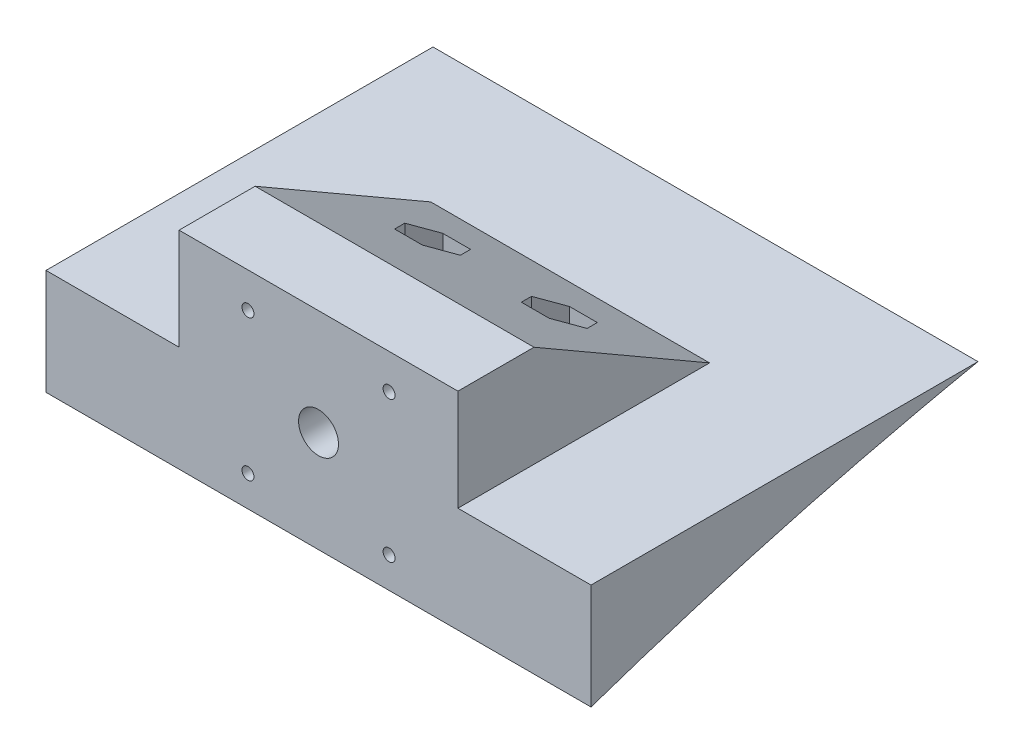
SolidWorks part; units mm, degrees
material "ABS"
ref_plane "Front Plane" through (0, 0, 0) normal (0, 0, 1) x (1, 0, 0)
ref_plane "Top Plane" through (0, 0, 0) normal (0, 1, 0) x (1, 0, 0)
ref_plane "Right Plane" through (0, 0, 0) normal (1, 0, 0) x (0, 0, -1)
curve "Curve1"
  spline degree 3 poles (0, 0.0012, 1.0003) (0, 0.0015, 0.9994) (0, 0.0028, 0.9958) (0, 0.0055, 0.9879) (0, 0.0099, 0.9747) (0, 0.0159, 0.9565) (0, 0.0233, 0.9333) (0, 0.0318, 0.9054) (0, 0.0411, 0.8731) (0, 0.051, 0.8366) (0, 0.0612, 0.7964) (0, 0.0713, 0.7528) (0, 0.0811, 0.7063) (0, 0.0903, 0.6574) (0, 0.0985, 0.6067) (0, 0.1057, 0.5546) (0, 0.1115, 0.5018) (0, 0.1158, 0.4488) (0, 0.1186, 0.3959) (0, 0.1189, 0.3436) (0, 0.1164, 0.2927) (0, 0.1112, 0.2442) (0, 0.1037, 0.1988) (0, 0.0942, 0.157) (0, 0.0831, 0.1194) (0, 0.0711, 0.0865) (0, 0.0584, 0.0585) (0, 0.0457, 0.0357) (0, 0.0334, 0.0184) (0, 0.0218, 0.0064) (0, 0.0108, -0.0005) (0, -0.0003, -0.0011) (0, -0.0092, 0.0055) (0, -0.0148, 0.017) (0, -0.0185, 0.0329) (0, -0.0204, 0.0533) (0, -0.0208, 0.0781) (0, -0.0198, 0.107) (0, -0.0176, 0.1398) (0, -0.0147, 0.176) (0, -0.0111, 0.2153) (0, -0.0074, 0.2574) (0, -0.0037, 0.3019) (0, -0.0005, 0.3484) (0, 0.002, 0.397) (0, 0.0037, 0.4471) (0, 0.0055, 0.4983) (0, 0.0069, 0.5496) (0, 0.0079, 0.6006) (0, 0.0085, 0.6505) (0, 0.0086, 0.699) (0, 0.0083, 0.7455) (0, 0.0076, 0.7894) (0, 0.0065, 0.8302) (0, 0.0053, 0.8675) (0, 0.0039, 0.9007) (0, 0.0027, 0.9296) (0, 0.0013, 0.9539) (0, 0.0006, 0.9727) (0, -0.0011, 0.9872) (0, 0, 0.9944) (0, -0.002, 0.9999) (0, -0.0005, 1) (0, 0, 1) knots 0 0 0 0 0.001372 0.005465 0.012235 0.021602 0.033461 0.047671 0.064081 0.082496 0.102719 0.124527 0.147676 0.171913 0.196978 0.222597 0.248497 0.274385 0.300041 0.32569 0.350525 0.37428 0.396711 0.417577 0.436654 0.453744 0.46868 0.481329 0.491631 0.499616 0.505546 0.510185 0.514824 0.520702 0.528516 0.538466 0.550543 0.564643 0.580638 0.598345 0.617584 0.638174 0.659922 0.682632 0.706121 0.730727 0.7557 0.780732 0.805564 0.829932 0.85357 0.876213 0.89761 0.917519 0.935698 0.951943 0.966047 0.97784 0.987174 0.993932 0.998018 0.999386 1 1 1 1
sketch "Sketch1" plane through (0, 0, 0) normal (1, 0, 0) x (0, 0, -1)
  line L3 (195.725, 0) -> (-195.725, 0) construction
  line L4 (71.5374, 26.4626) -> (-25.4, 26.4626)
  line L5 (-25.4, 26.4626) -> (-25.4, 0)
  spline S1 degree 3 poles (-25.4, 0) (-25.0834, 0.108) (-23.8218, 0.5382) (-20.9978, 1.5029) (-16.3151, 3.0589) (-6.5282, 6.2519) (9.8573, 11.2778) (28.9301, 16.5496) (47.1199, 21.0862) (60.1793, 24.0716) (68.4583, 25.8283) (71.5374, 26.4626) knots 0 0 0 0 0.001372 0.005465 0.012235 0.021602 0.047671 0.082496 0.102719 0.124527 0.137416 0.137416 0.137416 0.137416
  dimension "D1" = 26.4626
  dimension "D2" = 25.4
  dimension "D3" = 96.9374
extrude "Boss-Extrude1" add sketch "Sketch1" along normal mid plane 136.525
sketch "Sketch4" plane through (0, 0, 25.4) normal (0, 0, 1) x (1, 0, 0)
  line L0 (68.2625, 26.4626) -> (-68.2625, 26.4626) construction
  line L1 (-34.925, 51.8626) -> (34.925, 51.8626)
  line L2 (-34.925, 51.8626) -> (-34.925, 26.4626)
  line L3 (-34.925, 26.4626) -> (34.925, 26.4626)
  line L4 (34.925, 51.8626) -> (34.925, 26.4626)
  point P6 (0, 26.4626)
  dimension "D1" = 25.4
  dimension "D2" = 69.85
extrude "Boss-Extrude2" add sketch "Sketch4" against normal blind 50.8
sketch "Sketch2" plane through (0, 26.4626, 0) normal (0, 1, 0) x (1, 0, 0)
  line L0 (-68.2625, 19.05) -> (68.2625, 19.05) construction
  line L1 (-68.2625, 71.5374) -> (-68.2625, -25.4) construction
  line L2 (68.2625, 71.5374) -> (68.2625, -25.4) construction
  line L3 (-15.875, 19.05) -> (-15.875, 71.5374) construction
  line L4 (68.2625, 71.5374) -> (-68.2625, 71.5374) construction
  line L5 (15.875, 19.05) -> (15.875, 71.5374) construction
  line L6 (-68.2625, -286.8403) -> (-15.875, -286.8403) construction
  line L7 (-15.875, -286.8403) -> (15.875, -286.8403) construction
  line L8 (15.875, -286.8403) -> (68.2625, -286.8403) construction
  line L9 (-34.925, -25.4) -> (-68.2625, -25.4) construction
  circle A0 centre (-15.875, 19.05) radius 3.175
  circle A1 centre (15.875, 19.05) radius 3.175
  dimension "D1" = 6.35
  dimension "D2" = 6.35
  dimension "D3" = 31.75
  dimension "D4" = 44.45
extrude "Cut-Extrude1" cut sketch "Sketch2" against normal through all and the other way through all
sketch "Sketch5" plane through (0, 0, 25.4) normal (0, 0, 1) x (1, 0, 0)
  line L0 (68.2625, 0) -> (-68.2625, 0) construction
  circle A0 centre (0, 25.4) radius 5
  dimension "D1" = 10
  dimension "D2" = 25.4
extrude "Cut-Extrude2" cut sketch "Sketch5" against normal blind 12.7
sketch "Sketch6" plane through (0, 0, 25.4) normal (0, 0, 1) x (1, 0, 0)
  line L0 (0, 25.4) -> (27.6134, 53.0134) construction
  line L1 (0, 25.4) -> (45.1172, 25.4) construction
  circle A0 centre (17.6777, 43.0777) radius 1.5
  dimension "D1" = 3
  dimension "D2" = 25
  dimension "D3" = 45
extrude "Cut-Extrude3" cut sketch "Sketch6" against normal blind 6.35
pattern_circular "CirPattern1" count 4 over 360 about axis through (0, 25.4, 12.7) along (0, 0, 1) of "Cut-Extrude3"
sketch "Sketch7" plane through (-34.925, 0, 0) normal (-1, 0, 0) x (0, 0, 1)
  line L0 (-25.4, 51.8626) -> (-71.5374, 26.4626)
  line L1 (-71.5374, 26.4626) -> (25.4, 26.4626) construction
  line L2 (-71.5374, 26.4626) -> (-25.4, 26.4626)
  line L3 (-25.4, 26.4626) -> (-25.4, 51.8626)
  spline S0 degree 3 poles (25.4, 0) (25.0834, 0.108) (23.8218, 0.5382) (20.9978, 1.5029) (16.3151, 3.0589) (6.5282, 6.2519) (-9.8573, 11.2778) (-28.9301, 16.5496) (-47.1199, 21.0862) (-60.1793, 24.0716) (-68.4583, 25.8283) (-71.5374, 26.4626) knots 0 0 0 0 0.001372 0.005465 0.012235 0.021602 0.047671 0.082496 0.102719 0.124527 0.137416 0.137416 0.137416 0.137416 construction
extrude "Boss-Extrude3" add sketch "Sketch7" against normal up to surface (69.85 mm away) up to face at (34.925, 39.1626, 0)
sketch "Sketch8" plane through (0, 51.8626, 0) normal (0, 1, 0) x (1, 0, 0)
  circle A0 centre (15.875, 19.05) radius 6.35
  circle A1 centre (-15.875, 19.05) radius 6.35
  dimension "D1" = 12.7
extrude "Cut-Extrude4" cut sketch "Sketch8" against normal blind 6.35
sketch "Sketch9" plane through (-34.925, 0, 0) normal (-1, 0, 0) x (0, 0, 1)
  line L1 (-71.5374, 26.4626) -> (-37.6441, 26.4626)
  line L2 (-71.5374, 26.4626) -> (-71.5374, 51.8626)
  line L3 (-71.5374, 51.8626) -> (6.35, 51.8626)
  line L5 (-25.4, 51.8626) -> (25.4, 51.8626) construction
  line L6 (-37.6441, 26.4626) -> (6.35, 51.8626)
  line L7 (25.4, 51.8626) -> (25.4, 26.4626) construction
  dimension "D1" = 19.05
  dimension "D2" = 30
extrude "Cut-Extrude5" cut sketch "Sketch9" against normal through all both and the other way through all
sketch "Sketch10" plane through (0, 51.8626, 0) normal (0, 1, 0) x (1, 0, 0)
  line L1 (22.8407, 19.05) -> (19.3579, 25.0825)
  line L2 (19.3579, 25.0825) -> (12.3921, 25.0825)
  line L3 (12.3921, 25.0825) -> (8.9093, 19.05)
  line L4 (8.9093, 19.05) -> (12.3921, 13.0175)
  line L5 (12.3921, 13.0175) -> (19.3579, 13.0175)
  line L6 (19.3579, 13.0175) -> (22.8407, 19.05)
  line L7 (-8.9093, 19.05) -> (-12.3921, 25.0825)
  line L8 (-12.3921, 25.0825) -> (-19.3579, 25.0825)
  line L9 (-19.3579, 25.0825) -> (-22.8407, 19.05)
  line L10 (-22.8407, 19.05) -> (-19.3579, 13.0175)
  line L11 (-19.3579, 13.0175) -> (-12.3921, 13.0175)
  line L12 (-12.3921, 13.0175) -> (-8.9093, 19.05)
  circle A2 centre (15.875, 19.05) radius 6.0325 construction
  circle A3 centre (-15.875, 19.05) radius 6.0325 construction
  dimension "D1" = 12.065
  dimension "D2" = 12.065
extrude "Cut-Extrude6" cut sketch "Sketch10" against normal blind 29.21
